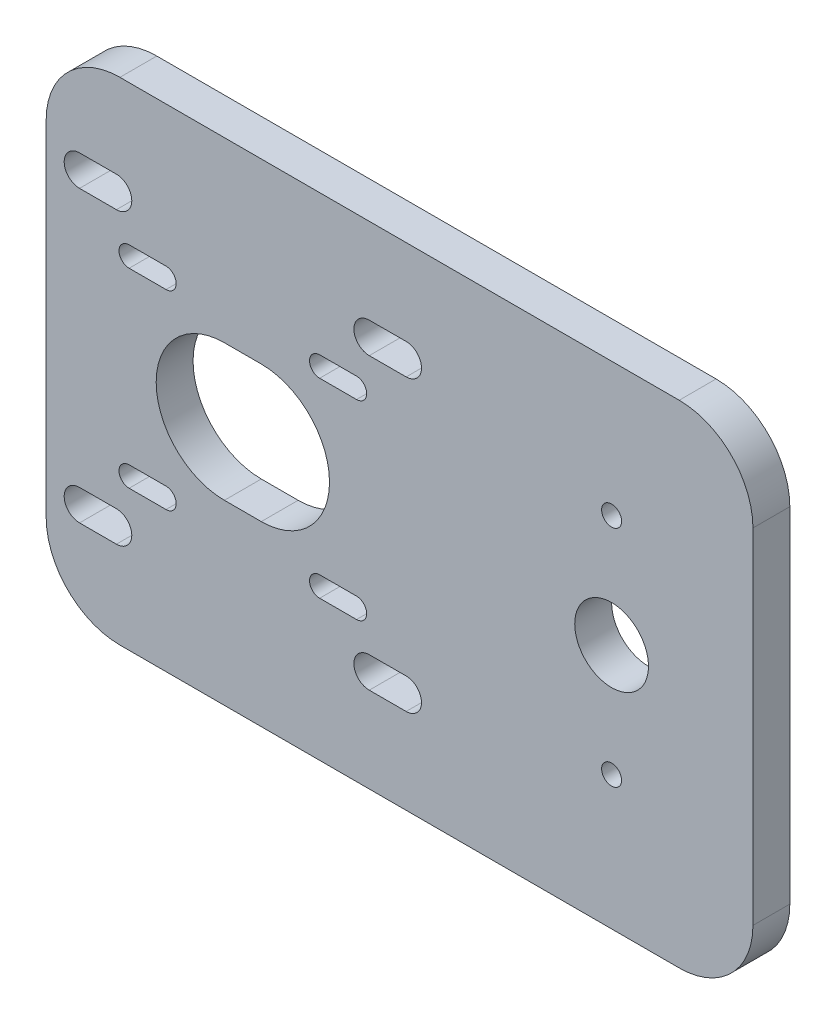
SolidWorks part; units mm, degrees
ref_plane "Alzado" through (0, 0, 0) normal (0, 0, 1) x (1, 0, 0)
ref_plane "Planta" through (0, 0, 0) normal (0, 1, 0) x (1, 0, 0)
ref_plane "Vista lateral" through (0, 0, 0) normal (1, 0, 0) x (0, 0, -1)
sketch "Croquis1" plane through (0, 0, 0) normal (0, 0, 1) x (1, 0, 0)
  line L1 (0, 0) -> (115, 0)
  line L2 (0, 0) -> (0, 80)
  line L3 (0, 80) -> (115, 80)
  line L4 (115, 0) -> (115, 80)
  dimension "D1" = 80
  dimension "D2" = 115
extrude "Saliente-Extruir1" add sketch "Croquis1" along normal blind 6
sketch "Croquis2" plane through (0, 0, 0) normal (0, 0, -1) x (-1, 0, 0)
  line L0 (0, 80) -> (0, 0) construction
  line L1 (0, 40) -> (-115, 40) construction
  line L4 (-115, 0) -> (-115, 80) construction
  line L7 (-29, 40) -> (-35, 40) construction
  line L10 (-29, 28.9) -> (-35, 28.9)
  line L19 (-29, 51.1) -> (-35, 51.1)
  line L20 (-13.5, 24.5) -> (-19.5, 24.5) construction
  line L21 (-13.5, 22.85) -> (-19.5, 22.85)
  line L22 (-13.5, 26.15) -> (-19.5, 26.15)
  line L23 (-44.5, 55.5) -> (-50.5, 55.5) construction
  line L24 (-44.5, 53.85) -> (-50.5, 53.85)
  line L25 (-44.5, 57.15) -> (-50.5, 57.15)
  line L26 (-44.5, 24.5) -> (-50.5, 24.5) construction
  line L27 (-44.5, 22.85) -> (-50.5, 22.85)
  line L28 (-44.5, 26.15) -> (-50.5, 26.15)
  line L29 (-13.5, 55.5) -> (-19.5, 55.5) construction
  line L30 (-13.5, 53.85) -> (-19.5, 53.85)
  line L31 (-13.5, 57.15) -> (-19.5, 57.15)
  line L32 (-92, 0) -> (-92, 80) construction
  line L33 (0, 0) -> (-115, 0) construction
  line L34 (-115, 80) -> (0, 80) construction
  line L35 (-61, 0) -> (-61, 80) construction
  line L36 (-52.57, 16.43) -> (-58.57, 16.43) construction
  line L37 (-52.57, 13.93) -> (-58.57, 13.93)
  line L38 (-52.57, 18.93) -> (-58.57, 18.93)
  line L39 (-5.43, 16.43) -> (-11.43, 16.43) construction
  line L40 (-5.43, 13.93) -> (-11.43, 13.93)
  line L41 (-5.43, 18.93) -> (-11.43, 18.93)
  line L42 (-52.57, 63.57) -> (-58.57, 63.57) construction
  line L43 (-52.57, 61.07) -> (-58.57, 61.07)
  line L44 (-52.57, 66.07) -> (-58.57, 66.07)
  line L45 (-5.43, 63.57) -> (-11.43, 63.57) construction
  line L46 (-5.43, 61.07) -> (-11.43, 61.07)
  line L47 (-5.43, 66.07) -> (-11.43, 66.07)
  circle A5 centre (-92, 40) radius 6
  circle A15 centre (-92, 21.75) radius 1.625
  circle A16 centre (-92, 58.25) radius 1.625
  arc A19 (-29, 28.9) -> (-29, 51.1) centre (-29, 40) ccw
  arc A20 (-35, 51.1) -> (-35, 28.9) centre (-35, 40) ccw
  arc A21 (-13.5, 22.85) -> (-13.5, 26.15) centre (-13.5, 24.5) ccw
  arc A22 (-19.5, 26.15) -> (-19.5, 22.85) centre (-19.5, 24.5) ccw
  arc A23 (-44.5, 53.85) -> (-44.5, 57.15) centre (-44.5, 55.5) ccw
  arc A24 (-50.5, 57.15) -> (-50.5, 53.85) centre (-50.5, 55.5) ccw
  arc A25 (-44.5, 22.85) -> (-44.5, 26.15) centre (-44.5, 24.5) ccw
  arc A26 (-50.5, 26.15) -> (-50.5, 22.85) centre (-50.5, 24.5) ccw
  arc A27 (-13.5, 53.85) -> (-13.5, 57.15) centre (-13.5, 55.5) ccw
  arc A28 (-19.5, 57.15) -> (-19.5, 53.85) centre (-19.5, 55.5) ccw
  arc A29 (-52.57, 13.93) -> (-52.57, 18.93) centre (-52.57, 16.43) ccw
  arc A30 (-58.57, 18.93) -> (-58.57, 13.93) centre (-58.57, 16.43) ccw
  arc A31 (-5.43, 13.93) -> (-5.43, 18.93) centre (-5.43, 16.43) ccw
  arc A32 (-11.43, 18.93) -> (-11.43, 13.93) centre (-11.43, 16.43) ccw
  arc A33 (-52.57, 61.07) -> (-52.57, 66.07) centre (-52.57, 63.57) ccw
  arc A34 (-58.57, 66.07) -> (-58.57, 61.07) centre (-58.57, 63.57) ccw
  arc A35 (-5.43, 61.07) -> (-5.43, 66.07) centre (-5.43, 63.57) ccw
  arc A36 (-11.43, 66.07) -> (-11.43, 61.07) centre (-11.43, 63.57) ccw
  point P6 (-32, 40)
  point P19 (-16.5, 24.5)
  point P28 (-47.5, 55.5)
  point P35 (-47.5, 24.5)
  point P41 (-55.57, 16.43)
  point P48 (-16.5, 55.5)
  point P63 (-8.43, 16.43)
  point P72 (-55.57, 63.57)
  point P79 (-8.43, 63.57)
  dimension "D2" = 6
  dimension "D3" = 11.1
  dimension "D4" = 3.3
  dimension "D5" = 6
  dimension "D6" = 12
  dimension "D13" = 3.25
  dimension "D14" = 3.25
  dimension "D29" = 2.5
  dimension "D32" = 2.5
  dimension "D34" = 2.5
  dimension "D36" = 2.5
  dimension "D7" = 15.5
  dimension "D8" = 15.5
  dimension "D9" = 3.3
  dimension "D10" = 6
  dimension "D11" = 23
  dimension "D12" = 40
  dimension "D15" = 18.25
  dimension "D16" = 18.25
  dimension "D17" = 3.3
  dimension "D18" = 6
  dimension "D19" = 3.3
  dimension "D20" = 6
  dimension "D21" = 15.5
  dimension "D22" = 15.5
  dimension "D23" = 15.5
  dimension "D24" = 15.5
  dimension "D25" = 15.5
  dimension "D26" = 15.5
  dimension "D27" = 60
  dimension "D28" = 26
  dimension "D30" = 6
  dimension "D31" = 6
  dimension "D33" = 6
  dimension "D35" = 6
  dimension "D37" = 23.57
  dimension "D38" = 23.57
  dimension "D39" = 23.57
  dimension "D40" = 23.57
  dimension "D41" = 23.57
  dimension "D42" = 23.57
  dimension "D43" = 23.57
  dimension "D44" = 23.57
extrude "Cortar-Extruir1" cut sketch "Croquis2" against normal through all
fillet "Redondeo1" radius 12 4 edges at (115, 0, 3) (115, 80, 3) (0, 0, 3) (0, 80, 3)
